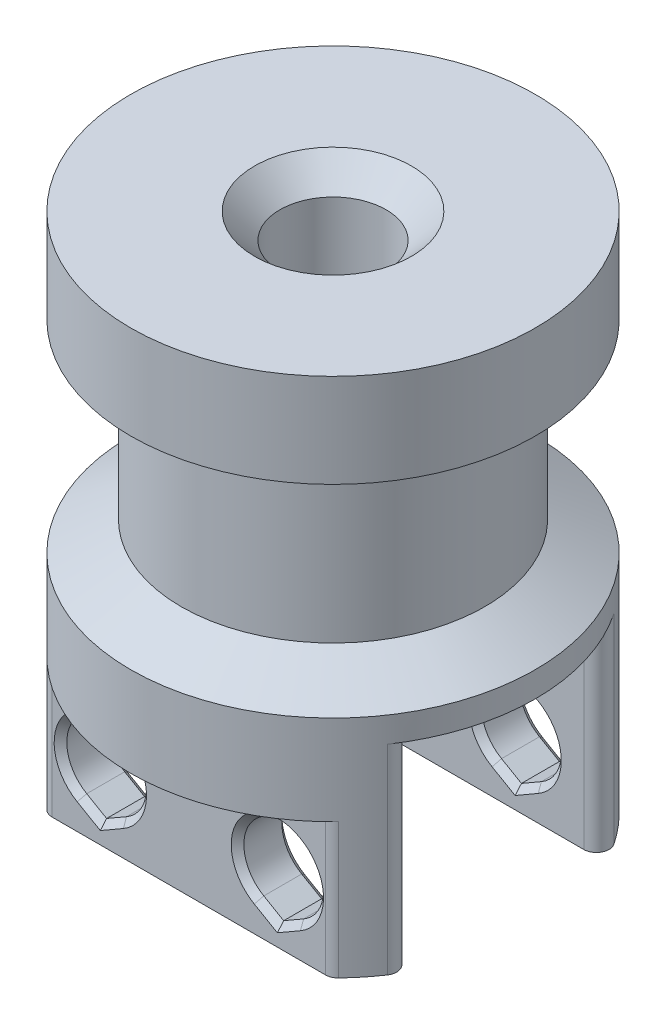
SolidWorks part; units mm, degrees
ref_plane "Front Plane" through (0, 0, 0) normal (0, 0, 1) x (1, 0, 0)
ref_plane "Top Plane" through (0, 0, 0) normal (0, 1, 0) x (1, 0, 0)
ref_plane "Right Plane" through (0, 0, 0) normal (1, 0, 0) x (0, 0, -1)
sketch "Sketch1" plane through (0, 0, 0) normal (0, 0, 1) x (1, 0, 0)
  line L0 (33.3564, -20.875) -> (39.2564, -20.875)
  line L1 (39.2564, -20.875) -> (39.2564, -24.575)
  line L2 (39.2564, -24.575) -> (37.2564, -24.575)
  line L3 (37.2564, -24.575) -> (37.2564, -30.575)
  line L4 (37.2564, -30.575) -> (39.2564, -30.575)
  line L5 (39.2564, -30.575) -> (39.2564, -33.575)
  line L6 (39.2564, -33.575) -> (33.3564, -33.575)
  line L7 (33.3564, -33.575) -> (33.3564, -20.875)
  line L8 (31.2564, 2.6544) -> (31.2564, -18.4582) construction
  line L9 (27.7564, -38.875) -> (34.7564, -38.875) construction
  line L10 (23.2564, -35.875) -> (39.2564, -35.875)
  line L11 (39.2564, -35.875) -> (39.2564, -41.475)
  line L12 (39.2564, -41.475) -> (23.2564, -41.475)
  line L13 (23.2564, -41.475) -> (23.2564, -35.875)
  line L14 (23.2564, -35.875) -> (31.2564, -83.175) construction
  line L15 (26.9689, -40.239) -> (27.7564, -40.6936)
  line L17 (39.2564, -36.125) -> (23.2564, -36.125)
  line L28 (27.7564, -40.6936) -> (28.5439, -40.239)
  line L29 (33.9689, -40.239) -> (34.7564, -40.6936)
  line L30 (34.7564, -40.6936) -> (35.5439, -40.239)
  line L31 (39.2564, -33.575) -> (39.2564, -35.875)
  line L32 (33.3564, -33.575) -> (23.2564, -33.575)
  line L33 (23.2564, -33.575) -> (23.2564, -35.875)
  circle A0 centre (27.7564, -38.875) radius 1.575
  circle A1 centre (34.7564, -38.875) radius 1.575
  circle A2 centre (27.7564, -38.875) radius 2.75 construction
  circle A3 centre (34.7564, -38.875) radius 2.75 construction
  point P17 (31.2564, -38.875)
  point P19 (31.2564, -35.875)
  point P22 (0, 0)
  dimension "D1" = 5.5
  dimension "D2" = 240
  dimension "D3" = 3.7
  dimension "D4" = 6
  dimension "v6_groove_c" = 3
  dimension "ptfe_hole_radius" = 2.1
  dimension "v6_groove_radius_major" = 8
  dimension "v6_groove_radius_minor" = 6
  dimension "bambu_mount_hole_z_offset" = 3
  dimension "bambu_mount_block_height" = 5.6
  dimension "bambu_height" = 47.3
  dimension "v6_height" = 62.3
  dimension "bambu_mount_hole_diameter" = 3.15
  dimension "bambu_mount_hole_distance" = 7
revolve "Revolve1" add sketch "Sketch1" angle 360 about L8 region at (35.9346, -27.1582, 0)
chamfer "Chamfer1" distance 2 angle 60 1 edges at (31.2564, -30.575, 8) first distance on face at (31.2564, -33.575, 8)
chamfer "Chamfer3" distance 1 angle 45 1 edges at (31.2564, -20.875, 2.1)
extrude "Boss-Extrude1" add sketch "Sketch1<3>" against normal up to surface and the other way up to surface contours L32 L33 L10 L31 L6 | L13 L12 L11 L17 A1 L30 L29 A0 L28 L15 | L17 L11 L10 L13 | A0 | A1 | A0 L15 L28 | A1 L29 L30 region at (31.2564, -34.725, 0) region at (31.2564, -36, 0) region at (31.2564, -38.7767, 0) region at (27.7564, -40.5029, 0) region at (27.7564, -38.875, 0) region at (34.7564, -40.5029, 0) region at (34.7564, -38.875, 0) up to face at (31.2564, -32.575, 8) other way up to face at (31.2564, -32.575, 8)
sketch "Sketch1<3>" plane through (0, 0, 0) normal (0, 0, 1) x (1, 0, 0) same geometry as "Sketch1"
extrude "Cut-Extrude1" cut sketch "Sketch1<4>" against normal mid plane 7.4 contours L13 L12 L11 L17 A1 L30 L29 A0 L28 L15 | A0 | A1 | A1 L29 L30 | A0 L15 L28 | L32 L33 L10 L31 L6 | L17 L11 L10 L13 region at (31.2564, -34.725, 0) region at (31.2564, -36, 0) region at (31.2564, -38.7767, 0) region at (27.7564, -40.5029, 0) region at (27.7564, -38.875, 0) region at (34.7564, -40.5029, 0) region at (34.7564, -38.875, 0)
sketch "Sketch1<4>" plane through (0, 0, 0) normal (0, 0, 1) x (1, 0, 0) same geometry as "Sketch1"
extrude "Cut-Extrude3" cut sketch "Sketch1<6>" against normal through all both and the other way through all contours A0 | A0 L15 L28 | A1 L29 L30 | A1 region at (27.7564, -40.5029, 0) region at (27.7564, -38.875, 0) region at (34.7564, -40.5029, 0) region at (34.7564, -38.875, 0)
sketch "Sketch1<6>" plane through (0, 0, 0) normal (0, 0, 1) x (1, 0, 0) same geometry as "Sketch1"
extrude "Cut-Extrude2" cut sketch "Sketch1<5>" against normal through all from offset 5.7 contours L13 L12 L11 L17 A1 L30 L29 A0 L28 L15 region at (31.2564, -38.7767, 0) offset against normal yes
sketch "Sketch1<5>" plane through (0, 0, 0) normal (0, 0, 1) x (1, 0, 0) same geometry as "Sketch1"
mirror "Mirror2" about plane through (0, 0, 0) normal (0, 0, 1) of "Cut-Extrude2"
fillet "Fillet2" radius 0.5 8 edges at (38.3494, -37.525, 3.7) (24.1635, -37.525, 3.7) (24.1635, -37.525, -3.7) (38.3494, -37.525, -3.7) (36.8698, -38.8, -5.7) (25.6431, -38.8, -5.7) (25.6431, -38.8, 5.7) (36.8698, -38.8, 5.7)
chamfer "Chamfer4" distance 0.25 angle 45 24 edges at (28.1502, -40.4663, 5.7) (27.3627, -40.4663, 5.7) (27.7564, -37.3, 5.7) (35.1502, -40.4663, 5.7) (34.3627, -40.4663, 5.7) (34.7564, -37.3, 5.7) (28.1502, -40.4663, -5.7) (27.3627, -40.4663, -5.7) (27.7564, -37.3, -5.7) (35.1502, -40.4663, -5.7) (34.3627, -40.4663, -5.7) (34.7564, -37.3, -5.7) (28.1502, -40.4663, -3.7) (27.3627, -40.4663, -3.7) (27.7564, -37.3, -3.7) (35.1502, -40.4663, -3.7) (34.3627, -40.4663, -3.7) (34.7564, -37.3, -3.7) (28.1502, -40.4663, 3.7) (27.3627, -40.4663, 3.7) (27.7564, -37.3, 3.7) (35.1502, -40.4663, 3.7) (34.3627, -40.4663, 3.7) (34.7564, -37.3, 3.7)
equation "\"v6_height\"= 62.3"
equation "\"v6_groove_a\"= 3.7"
equation "\"v6_groove_b\"= 6"
equation "\"v6_groove_c\"= 3"
equation "\"v6_groove_radius_major\"= 8"
equation "\"v6_groove_radius_minor\"= 6"
equation "\"bambu_height\"= 47.3"
equation "\"bambu_mount_hole_diameter\"= 3.15"
equation "\"bambu_mount_block_depth\"= 7.4"
equation "\"bambu_mount_hole_distance\"= 7"
equation "\"bambu_mount_block_height\"= 6.6 - 1"
equation "\"bambu_mount_hole_z_offset\"= 3"
equation "\"ptfe_hole_radius\" = 4.2 / 2"
equation "\"D1\" = \"bambu_mount_block_depth\""
equation "\"D19\" = 2"
equation "\"D1@Cut-Extrude1\"=\"bambu_mount_block_depth\""
equation "\"D19@Cut-Extrude2\"=\"bambu_mount_block_depth\"/2 + 2"
